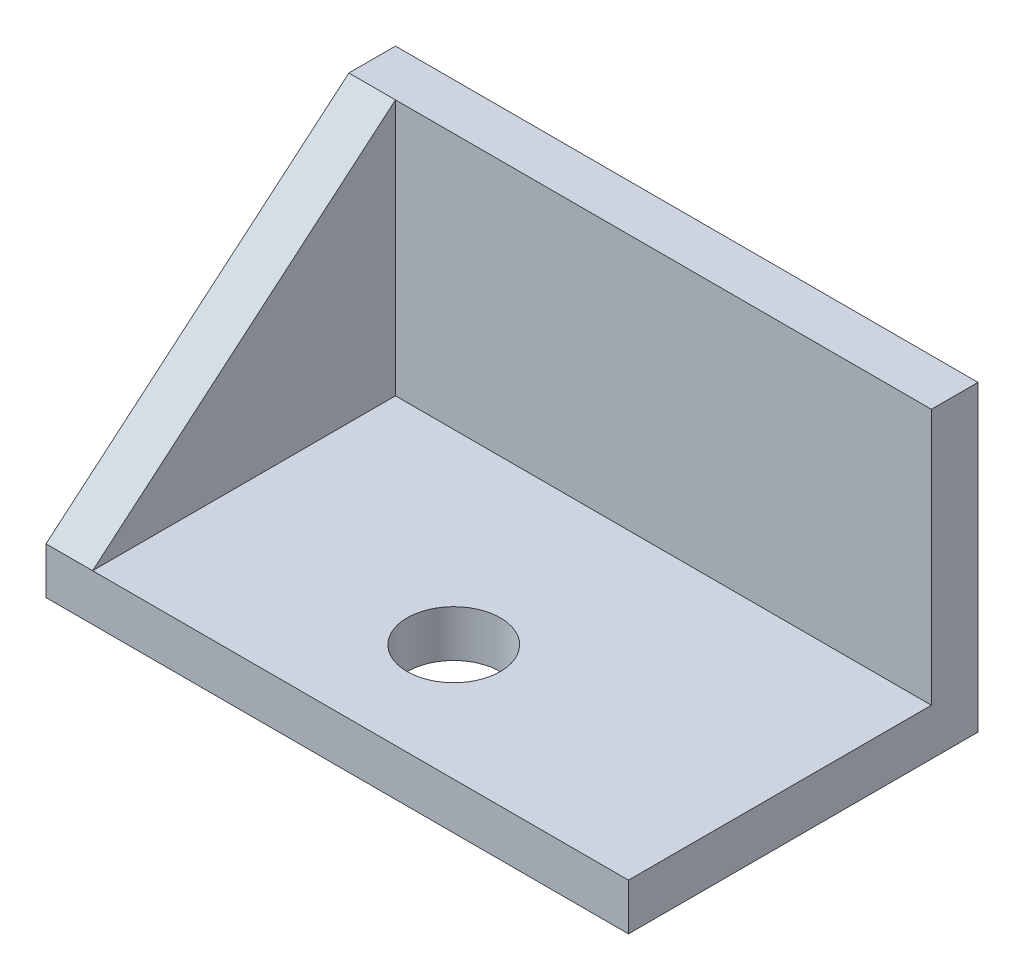
SolidWorks part; units mm, degrees
ref_plane "Front Plane" through (0, 0, 0) normal (0, 0, 1) x (1, 0, 0)
ref_plane "Top Plane" through (0, 0, 0) normal (0, 1, 0) x (1, 0, 0)
ref_plane "Right Plane" through (0, 0, 0) normal (1, 0, 0) x (0, 0, -1)
sketch "Sketch1" plane through (0, 0, 0) normal (0, 1, 0) x (1, 0, 0)
  line L0 (0, 0) -> (0, -75)
  line L1 (0, -75) -> (125, -75)
  line L2 (125, -75) -> (125, 0)
  line L3 (125, 0) -> (0, 0)
  line L4 (125, -75) -> (62.5, -75)
  line L5 (62.5, -75) -> (62.5, -50)
  circle A0 centre (62.5, -50) radius 10
extrude "Boss-Extrude2" add sketch "Sketch1" along normal blind 10 contours A0 L1 L2 L3 L0 region at (62.5, 0, 37.0666)
sketch "Sketch2" plane through (0, 0, 0) normal (-1, 0, 0) x (0, 0, 1)
  line L0 (0, 0) -> (0, 65)
  line L1 (0, 65) -> (10, 65)
  line L2 (10, 65) -> (10, 0)
  line L3 (0, 0) -> (75, 0) construction
  line L4 (0, 0) -> (75, 0)
  line L5 (75, 0) -> (75, 10)
  line L6 (75, 10) -> (10, 65)
  line M3 (75, 10) -> (0, 10)
extrude "Boss-Extrude3" add sketch "Sketch2" against normal blind 125 contours L2 L1 L0 M3 region at (0, 37.5, 5)
extrude "Boss-Extrude4" add sketch "Sketch2<3>" against normal blind 10 contours L6 L2 M3 region at (0, 28.3333, 31.6667)
sketch "Sketch2<3>" plane through (0, 0, 0) normal (-1, 0, 0) x (0, 0, 1) same geometry as "Sketch2"
